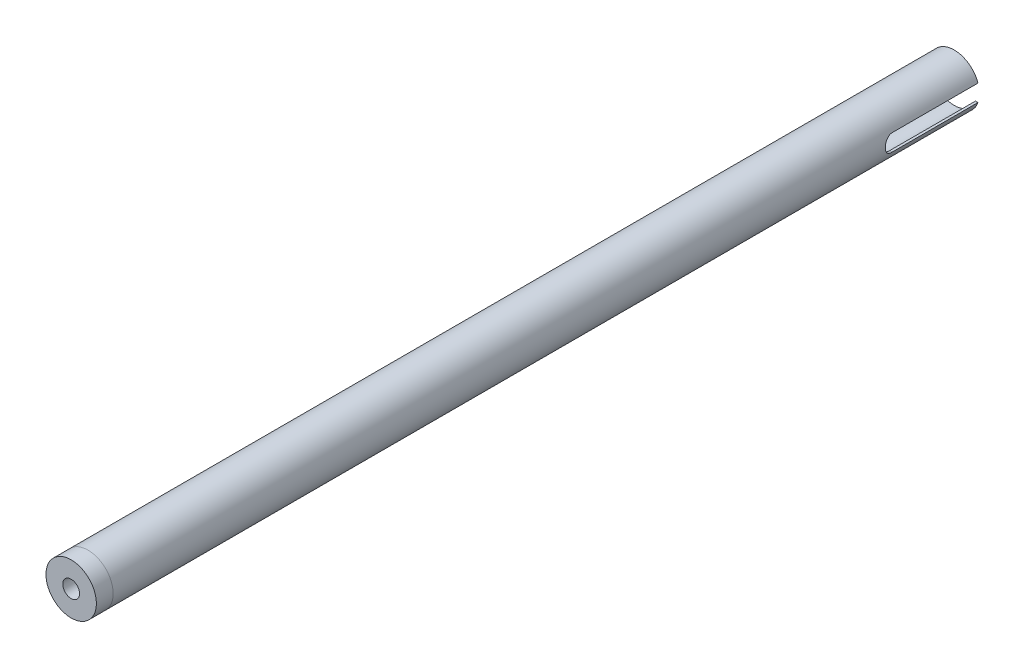
SolidWorks part; units mm, degrees
material "AISI 4130 Steel, normalized at 870C"
ref_plane "Front Plane" through (0, 0, 0) normal (0, 0, 1) x (1, 0, 0)
ref_plane "Top Plane" through (0, 0, 0) normal (0, 1, 0) x (1, 0, 0)
ref_plane "Right Plane" through (0, 0, 0) normal (1, 0, 0) x (0, 0, -1)
sketch "Axis" plane through (0, 0, 0) normal (0, 1, 0) x (1, 0, 0)
  line L0 (0, 0) -> (0, 333.5734) construction
  line L1 (0, 0) -> (0, -21.9075) construction
  line L2 (0, 333.5734) -> (-9.525, 333.5734) construction
  line L3 (0, 368.0751) -> (-10.3187, 330.6983) construction
  dimension "D1" = 21.9075
  dimension "D2" = 9.525
sketch "Sketch1" plane through (0, 0, 0) normal (0, 0, 1) x (1, 0, 0)
  line L0 (-9.525, 0) -> (9.525, 0) construction
  line L1 (-8.9803, 3.175) -> (8.9803, 3.175)
  line L2 (-8.9803, -3.175) -> (8.9803, -3.175)
  circle A0 centre (0, 0) radius 9.525
  circle A1 centre (0, 0) radius 8.636
  circle A2 centre (0, 0) radius 3.175
  dimension "D1" = 19.05
  dimension "D3" = 6.35
  dimension "D2" = 0.889
  dimension "D4" = 6.35
extrude "Threaded insert 1-1" add sketch "Sketch1" against normal blind 6.35 contours A2 L1 A1 | A1 L1 A0 | A2 L0 A1 L1 | A1 L0 A0 L1 | L0 A1 L2 A0 | L0 A2 L2 A1 | A2 L2 A1 | A1 L2 A0 | L0 A1 L2 A2 | L0 A0 L2 A1 | A0 L0 A1 L1 | A1 L0 A2 L1 region at (5.4259, 1.6615, 0) region at (5.4259, -1.6615, 0) region at (8.8881, 1.6046, 0) region at (8.8881, -1.6046, 0) region at (-5.4259, -1.6615, 0) region at (-5.4259, 1.6615, 0) region at (0, 5.4321, 0) region at (0, -5.4321, 0) region at (0, 8.8265, 0) region at (8.5057, -3.3655, 0) region at (-8.8881, -1.6046, 0) region at (-8.8881, 1.6046, 0)
extrude "Threaded insert 1-2" add sketch "Sketch1<3>" against normal blind 6.35 from surface contours A2 L1 A1 | A2 L0 A1 L1 | L0 A2 L2 A1 | A2 L2 A1 | L0 A1 L2 A2 | A1 L0 A2 L1 region at (5.4259, 1.6615, 0) region at (5.4259, -1.6615, 0) region at (-5.4259, -1.6615, 0) region at (-5.4259, 1.6615, 0) region at (0, 5.4321, 0) region at (0, -5.4321, 0) starting at face at (9.525, 0, -6.35)
sketch "Sketch1<3>" plane through (0, 0, 0) normal (0, 0, 1) x (1, 0, 0) same geometry as "Sketch1"
extrude "A-arm tube" add sketch "Sketch1<4>" against normal up to vertex (333.5734 mm away) from surface separate body contours A1 L1 A0 | A1 L0 A0 L1 | L0 A1 L2 A0 | A1 L2 A0 | L0 A0 L2 A1 | A0 L0 A1 L1 region at (8.8881, 1.6046, 0) region at (8.8881, -1.6046, 0) region at (0, 8.8265, 0) region at (8.5057, -3.3655, 0) region at (-8.8881, -1.6046, 0) region at (-8.8881, 1.6046, 0) up to point (0, 0, -333.5734) starting at face at (8.636, 0, -6.35)
sketch "Sketch1<4>" plane through (0, 0, 0) normal (0, 0, 1) x (1, 0, 0) same geometry as "Sketch1"
extrude "Apex slot" cut sketch "Sketch1<5>" along normal blind 35.56 from surface contours A0 L0 A1 L1 | L0 A0 L2 A1 | A1 L0 A0 L1 | L0 A1 L2 A0 region at (8.8881, 1.6046, 0) region at (8.8881, -1.6046, 0) region at (-8.8881, -1.6046, 0) region at (-8.8881, 1.6046, 0) starting at face at (8.636, 0, -333.5734)
sketch "Sketch1<5>" plane through (0, 0, 0) normal (0, 0, 1) x (1, 0, 0) same geometry as "Sketch1"
fillet "Fillet1" radius 3.175 4 edges at (-8.5057, 3.175, -298.0134) (-8.5057, -3.175, -298.0134) (8.5057, -3.175, -298.0134) (8.5057, 3.175, -298.0134)
equation "\"tube diameter\"= 3 / 4"
equation "\"tube thickness\"= .035"
equation "\"apex thickness\"= .25"
equation "\"tube slot\"= 1.4"
equation "\"D1@Sketch1\"=\"tube diameter\""
equation "\"D2@Sketch1\"=\"tube thickness\""
equation "\"threaded insert hole\"= 1 / 4"
equation "\"D3@Sketch1\"=\"threaded insert hole\""
equation "\"D4@Sketch1\"=\"apex thickness\""
equation "\"D1@Apex slot\" = \"tube slot\""
equation "\"D1@Fillet1\"=\"apex thickness\"/2"
equation "\"D2@Axis\"=\"tube diameter\"/2"
